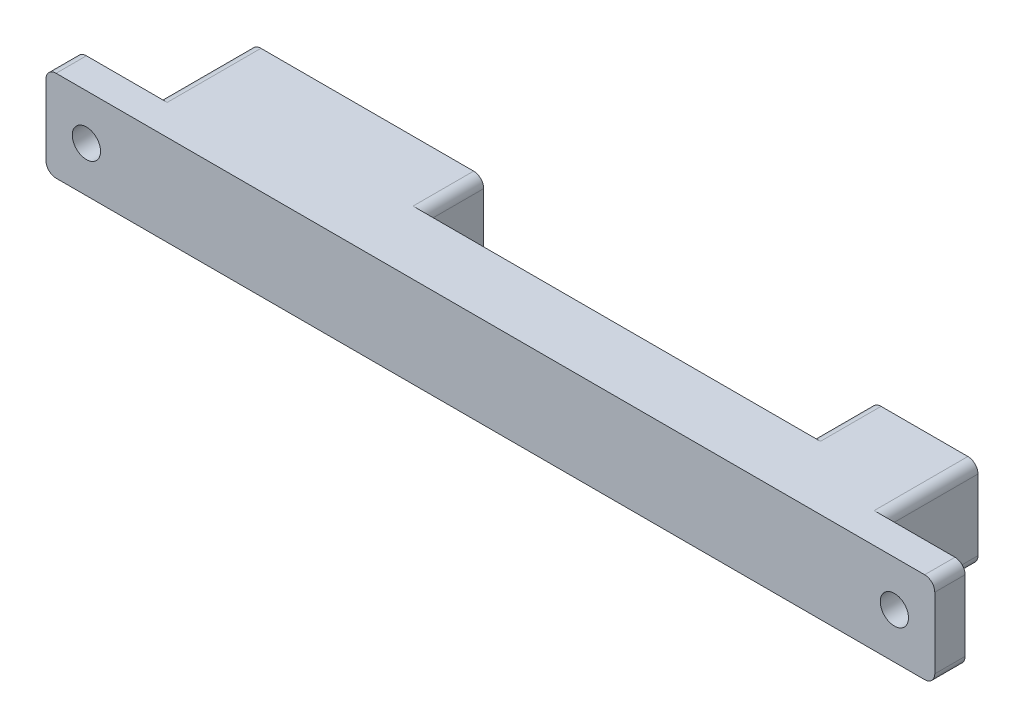
SolidWorks part; units mm, degrees
ref_plane "Front Plane" through (0, 0, 0) normal (0, 0, 1) x (1, 0, 0)
ref_plane "Top Plane" through (0, 0, 0) normal (0, 1, 0) x (1, 0, 0)
ref_plane "Right Plane" through (0, 0, 0) normal (1, 0, 0) x (0, 0, -1)
sketch "Sketch1" plane through (0, 0, 0) normal (0, 0, 1) x (1, 0, 0)
  line L1 (-36, 28.4) -> (36, 28.4)
  line L2 (-36, 28.4) -> (-36, 19.4)
  line L3 (-36, 19.4) -> (36, 19.4)
  line L4 (36, 28.4) -> (36, 19.4)
  line L12 (-12.94, 20.4) -> (-12.94, 27.4)
  line L13 (-12.94, 19.4) -> (-12.94, 28.4)
  line L14 (35, 28.4) -> (35, 7) construction
  line L15 (25.4, 20.4) -> (25.4, 27.4)
  line L16 (25.4, 19.4) -> (25.4, 28.4)
  line L17 (-35, 28.4) -> (-35, 7) construction
  line L19 (-35, 28.4) -> (35, 28.4) construction
  circle A0 centre (32, 23.9) radius 1.4 construction
  circle A1 centre (32, 23.9) radius 1.4 construction
  circle A2 centre (-32, 23.9) radius 1.4 construction
  circle A3 centre (-32, 23.9) radius 1.4 construction
  circle A4 centre (-32, 23.9) radius 1.8
  circle A5 centre (32, 23.9) radius 1.8
  dimension "D6" = 3.6
  dimension "D1" = 9
  dimension "D4" = 1
  dimension "D5" = 1
  dimension "D2" = 1
  dimension "D3" = 1
extrude "Boss-Extrude1" add sketch "Sketch1" along normal up to surface (12.28 mm away) contours A5 | L16 L3 L4 L1 A5 | L3 L13 L1 L2 A4 | A4 | L3 L16 L1 L13 region at (-24.0816, 23.9, 0) region at (6.23, 23.9, 0) region at (30.7, 28.2609, 0) region at (-32, 23.9, 0) region at (32, 23.9, 0)
extrude "Cut-Extrude1" cut sketch "Sketch1<3>" along normal blind 6 contours L3 L16 L1 L13 region at (6.23, 23.9, 0)
sketch "Sketch1<3>" plane through (0, 0, 0) normal (0, 0, 1) x (1, 0, 0) same geometry as "Sketch1"
extrude "Cut-Extrude2" cut sketch "Sketch1<4>" along normal blind 8 contours A4 | A5 region at (-32, 23.9, 0) region at (32, 23.9, 0)
sketch "Sketch1<4>" plane through (0, 0, 0) normal (0, 0, 1) x (1, 0, 0) same geometry as "Sketch1"
sketch "Sketch2" plane through (0, 0, 12.28) normal (0, 0, 1) x (1, 0, 0)
  line L0 (36, 19.4) -> (36, 28.4)
  line L1 (36, 19.4) -> (44, 19.4)
  line L2 (36, 28.4) -> (44, 28.4)
  line L3 (44, 19.4) -> (44, 28.4)
  line L4 (-36, 19.4) -> (-36, 28.4)
  line L5 (-36, 19.4) -> (-44, 19.4)
  line L6 (-36, 28.4) -> (-44, 28.4)
  line L7 (-44, 19.4) -> (-44, 28.4)
  line L8 (-44, 19.4) -> (-36, 28.4) construction
  line L9 (36, 19.4) -> (44, 28.4) construction
  circle A0 centre (-40, 23.9) radius 1.4
  circle A1 centre (40, 23.9) radius 1.4
  line M9 (-36, 28.4) -> (-36, 19.4)
  line M11 (36, 19.4) -> (36, 28.4)
  dimension "D2" = 2.8
  dimension "D1" = 8
extrude "Boss-Extrude2" add sketch "Sketch2" against normal blind 3 contours L7 L5 L6 A0 M9 | L1 L3 L2 A1 M11 region at (36.1204, 23.9, 12.28) region at (-40, 19.5204, 12.28)
fillet "Fillet1" radius 1 12 edges at (-12.94, 28.4, 3) (-12.94, 19.4, 3) (25.4, 28.4, 3) (25.4, 19.4, 3) (36, 28.4, 4.64) (36, 19.4, 4.64) (44, 19.4, 10.78) (44, 28.4, 10.78) (-36, 19.4, 4.64) (-36, 28.4, 4.64) (-44, 28.4, 10.78) (-44, 19.4, 10.78)
chamfer "Chamfer1" distance 0.5 angle 45 2 edges at (33.8, 23.9, 0) (-30.2, 23.9, 0)
